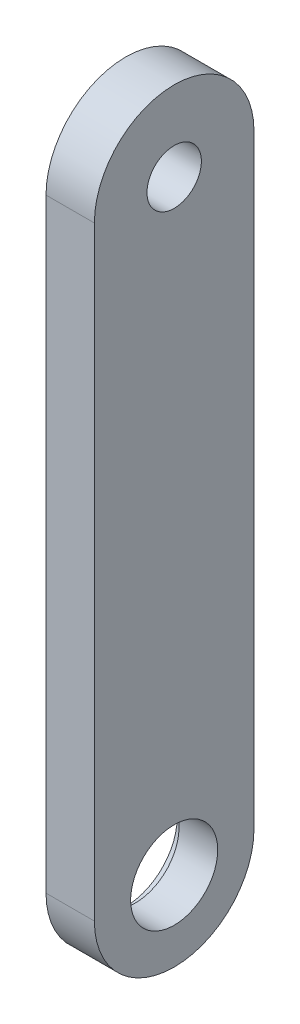
SolidWorks part; units mm, degrees
ref_plane "Front Plane" through (0, 0, 0) normal (1, 0, 0) x (0, 1, 0)
ref_plane "Top Plane" through (0, 0, 0) normal (0, 0, 1) x (0, 1, 0)
ref_plane "Right Plane" through (0, 0, 0) normal (0, 1, 0) x (-1, 0, 0)
sketch "Sketch2" plane through (0, 0, 0) normal (1, 0, 0) x (0, 1, 0)
  line L0 (0, 0) -> (3.6, 0)
  line L1 (0, 6.6) -> (50, 6.6)
  line L2 (0, -6.6) -> (50, -6.6)
  line L3 (47.75, 0) -> (50, 0)
  circle A0 centre (0, 0) radius 3.6
  circle A1 centre (50, 0) radius 2.25
  arc A2 (0, 6.6) -> (0, -6.6) centre (0, 0) ccw
  arc A3 (50, -6.6) -> (50, 6.6) centre (50, 0) ccw
  circle A4 centre (0, 0) radius 6.6 construction
  circle A5 centre (50, 0) radius 6.6 construction
  dimension "D1" = 7.2
  dimension "D2" = 4.5
  dimension "D5" = 50
  dimension "D3" = 3
extrude "Boss-Extrude1" add sketch "Sketch2" along normal mid plane 4 contours L2 A3 L1 A2 A0 A1 region at (0, 25.8379, 0)
sketch "Sketch3" plane through (-2, 0, 0) normal (1, 0, 0) x (0, 1, 0)
  circle A0 centre (0, 0) radius 4.25
  dimension "D1" = 8.5
extrude "Cut-Extrude1" cut sketch "Sketch3" along normal blind 0.8
